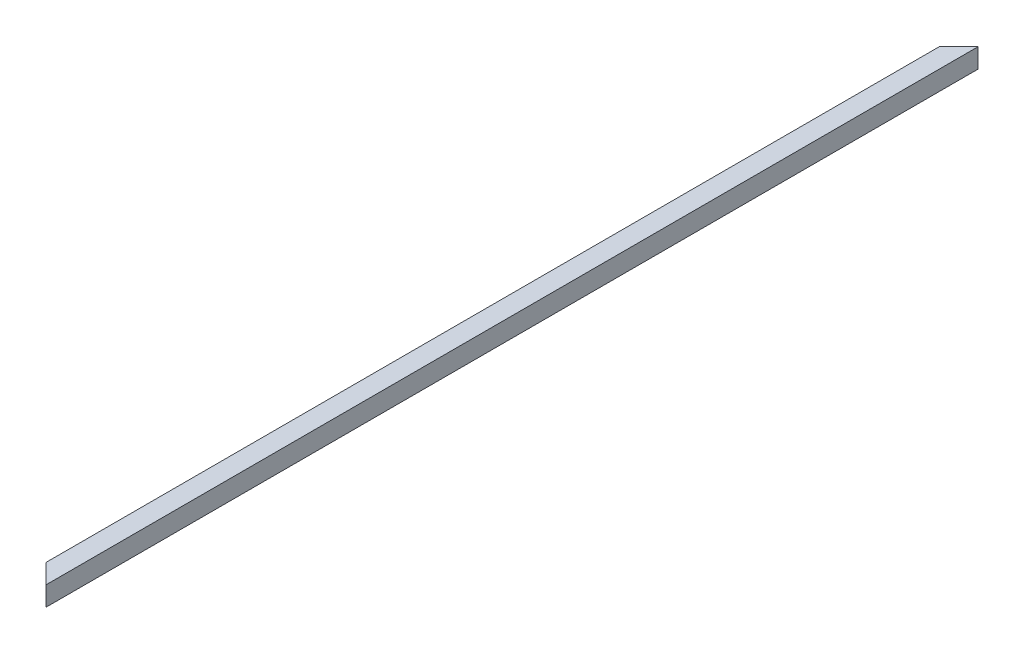
SolidWorks part; units mm, degrees
ref_plane "Front Plane" through (0, 0, 0) normal (0, 0, 1) x (1, 0, 0)
ref_plane "Top Plane" through (0, 0, 0) normal (0, 1, 0) x (1, 0, 0)
ref_plane "Right Plane" through (0, 0, 0) normal (1, 0, 0) x (0, 0, -1)
sketch "Sketch1" plane through (0, 0, 0) normal (0, 0, 1) x (1, 0, 0)
  line L0 (0, 0) -> (0, -25.4)
  line L9 (0, -25.4) -> (-6.35, -25.4)
  line L10 (-6.35, -25.4) -> (-6.35, -6.35)
  line L11 (-6.35, -6.35) -> (-25.4, -6.35)
  line L12 (-25.4, -6.35) -> (-25.4, 0)
  line L13 (-25.4, 0) -> (0, 0)
  point P2 (-34.161, 1.8512)
  point P8 (0, 0)
  point P9 (-4.4683, -4.4683)
  dimension "D1" = 25.4
  dimension "D2" = 25.4
  dimension "D3" = 6.35
extrude "Boss-Extrude1" add sketch "Sketch1" along normal blind 1219.2
chamfer "Chamfer1" distance 25.4 angle 45 2 edges at (-25.4, -3.175, 0) (-25.4, -3.175, 1219.2)
